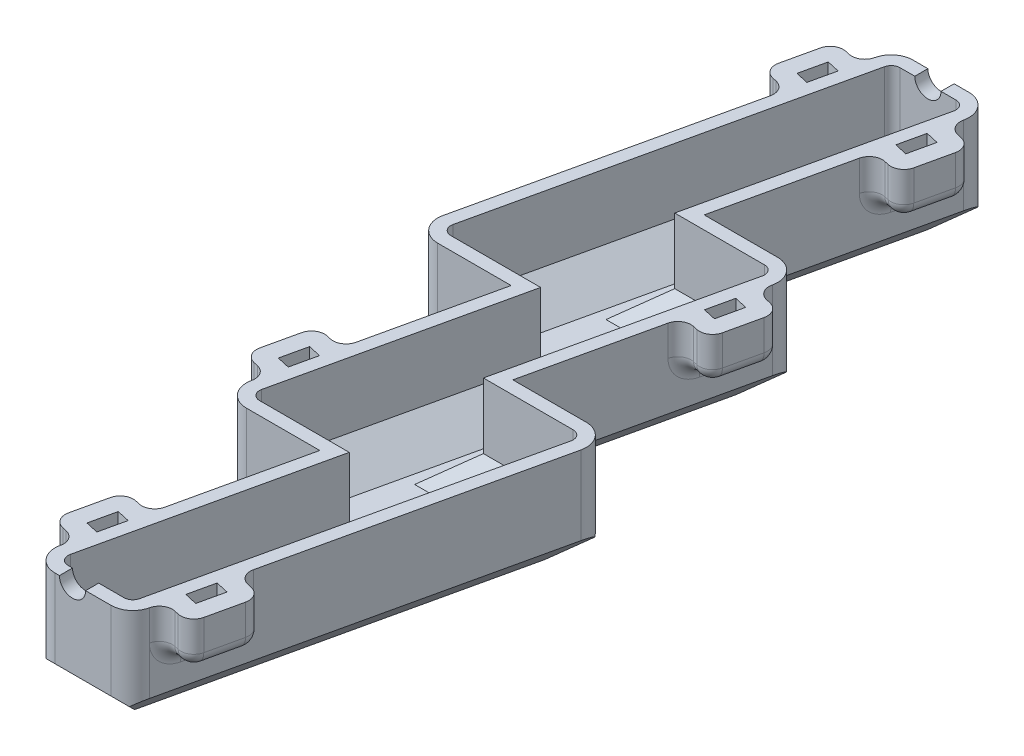
SolidWorks part; units mm, degrees
ref_plane "Front Plane" through (0, 0, 0) normal (0, 0, 1) x (1, 0, 0)
ref_plane "Top Plane" through (0, 0, 0) normal (0, 1, 0) x (1, 0, 0)
ref_plane "Right Plane" through (0, 0, 0) normal (1, 0, 0) x (0, 0, -1)
sketch "Sketch1" plane through (0, 0, 0) normal (0, 1, 0) x (1, 0, 0)
  line L12 (-1.3505, 45.3722) -> (21.7087, 45.3722)
  line L17 (-1.3505, 45.3722) -> (-21.7087, -45.3722)
  line L18 (21.7087, 45.3722) -> (1.3505, -45.3722)
  line L19 (-21.7087, -45.3722) -> (1.3505, -45.3722)
  line L20 (10.1791, 45.3722) -> (-10.1791, -45.3722) construction
  line L21 (12.1543, -100) -> (-10.905, -100)
  line L22 (12.1543, -100) -> (32.5125, -9.2556)
  line L23 (-10.905, -100) -> (9.4532, -9.2556)
  line L24 (32.5125, -9.2556) -> (9.4532, -9.2556)
  line L25 (0.6246, -100) -> (20.9828, -9.2556) construction
  line L26 (-12.1543, 100) -> (10.905, 100)
  line L27 (-12.1543, 100) -> (-32.5125, 9.2556)
  line L28 (10.905, 100) -> (-9.4532, 9.2556)
  line L29 (-32.5125, 9.2556) -> (-9.4532, 9.2556)
  line L30 (-0.6246, 100) -> (-20.9828, 9.2556) construction
  line L31 (-17.9611, -42.3722) -> (-1.051, -42.3722) construction
  line L32 (-17.9611, -42.3722) -> (1.051, 42.3722) construction
  line L33 (-1.051, -42.3722) -> (17.9611, 42.3722)
  line L34 (1.051, 42.3722) -> (17.9611, 42.3722) construction
  line L35 (9.5061, 42.3722) -> (17.556, 40.5662) construction
  line L36 (-9.4532, 9.2556) -> (9.4532, -9.2556) construction
  line L41 (1.3505, -45.3722) -> (20.2569, -63.8834) construction
  point P7 (0, 0)
  point P20 (9.5061, 42.3722)
  point P21 (-9.5061, -42.3722)
  point P26 (8.4551, 0)
  point P28 (0, 0)
  point P30 (10.8037, -54.6278)
  point P36 (10.8037, -54.6278)
  dimension "D1" = 93
  dimension "D2" = 16.5
  dimension "D3" = 85
  dimension "D4" = 3
  dimension "D5" = 3
  dimension "D6" = 200
extrude "Boss-Extrude1" add sketch "Sketch1" along normal blind 25
sketch "Sketch4" plane through (0, 25, 0) normal (0, 1, 0) x (1, 0, 0)
  line L8 (-9.7527, 97) -> (7.1574, 97)
  line L13 (-9.7527, 97) -> (-28.7648, 12.2556)
  line L18 (7.1574, 97) -> (-11.8547, 12.2556)
  line L19 (-28.7648, 12.2556) -> (-11.8547, 12.2556)
  line L20 (1.051, 42.3722) -> (17.9611, 42.3722)
  line L21 (1.051, 42.3722) -> (-17.9611, -42.3722)
  line L22 (17.9611, 42.3722) -> (-1.051, -42.3722)
  line L23 (-17.9611, -42.3722) -> (-1.051, -42.3722)
  line L24 (11.8547, -12.2556) -> (28.7648, -12.2556)
  line L25 (11.8547, -12.2556) -> (-7.1574, -97)
  line L30 (28.7648, -12.2556) -> (9.7527, -97)
  line L31 (-7.1574, -97) -> (9.7527, -97)
  line L34 (1.051, 42.3722) -> (-5.0982, 42.3722)
  line L35 (-11.8547, 12.2556) -> (-5.7056, 12.2556)
  line L36 (11.8547, -12.2556) -> (5.7056, -12.2556)
  line L37 (-1.051, -42.3722) -> (5.0982, -42.3722)
  line L39 (-12.1543, 100) -> (-32.5125, 9.2556) construction
  line L40 (10.905, 100) -> (-1.3505, 45.3722) construction
  line L41 (-9.4532, 9.2556) -> (-21.7087, -45.3722) construction
  line L42 (1.3505, -45.3722) -> (-10.905, -100) construction
  line L44 (-12.1543, 100) -> (10.905, 100) construction
  line L45 (-1.3505, 45.3722) -> (21.7087, 45.3722) construction
  line L46 (32.5125, -9.2556) -> (9.4532, -9.2556) construction
  line L47 (-32.5125, 9.2556) -> (-9.4532, 9.2556) construction
  dimension "D1" = 3
  dimension "D2" = 3
  dimension "D3" = 3
  dimension "D4" = 3
  dimension "D5" = 3
  dimension "D6" = 3
  dimension "D7" = 3
  dimension "D8" = 3
extrude "Cut-Extrude1" cut sketch "Sketch4" against normal blind 22 contours L13 L19 L18 L8 | L18 L35 L21 L34 | L21 L23 L22 L20 | L25 L31 L30 L24 | L22 L37 L25 L36
chamfer "Chamfer2" distance 7 angle 45 24 edges at (0.6246, 0, 100) (-4.7772, 0, 72.6861) (-10.1791, 0, 45.3722) (-15.581, 0, 18.0583) (-20.9828, 0, -9.2556) (-22.3334, 0, -54.6278) (-0.6246, 0, -100) (4.7772, 0, -72.6861) (10.1791, 0, -45.3722) (15.581, 0, -18.0583) (20.9828, 0, 9.2556) (22.3334, 0, 54.6278) (-19.2588, 3, -54.6278) (6.4315, 3, -42.3722) (17.2352, 3, 12.2556) (1.2977, 3, 97) (-1.0296, 3, 69.6861) (-6.4315, 3, 42.3722) (-11.8333, 3, 15.0583) (-17.2352, 3, -12.2556) (-1.2977, 3, -97) (1.0296, 3, -69.6861) (11.8333, 3, -15.0583) (19.2588, 3, 54.6278)
fillet "Fillet4" radius 5 8 edges at (12.1543, 16, 100) (-10.905, 16, 100) (-21.7087, 16, 45.3722) (-32.5125, 16, -9.2556) (-12.1543, 16, -100) (10.905, 16, -100) (21.7087, 16, -45.3722) (32.5125, 16, 9.2556)
fillet "Fillet5" radius 2 8 edges at (17.9611, 17.5, -42.3722) (9.7527, 17.5, 97) (-7.1574, 17.5, 97) (28.7648, 17.5, 12.2556) (-17.9611, 17.5, 42.3722) (-28.7648, 17.5, -12.2556) (-9.7527, 17.5, -97) (7.1574, 17.5, -97)
sketch "Sketch29" plane through (0, 25, 0) normal (0, 1, 0) x (1, 0, 0)
  line L0 (8.881, 90.9782) -> (8.0054, 87.0753)
  line L1 (8.881, 90.9782) -> (15.7112, 89.4459)
  line L2 (5.8163, 77.3178) -> (12.6466, 75.7855)
  line L3 (15.7112, 89.4459) -> (12.6466, 75.7855)
  line L4 (9.5377, 93.9055) -> (-1.3505, 45.3722) construction
  line L5 (-13.6872, 93.1673) -> (-14.5628, 89.2643)
  line L6 (-13.6872, 93.1673) -> (-20.5174, 94.6996)
  line L7 (-16.7518, 79.5068) -> (-23.582, 81.0392)
  line L8 (-20.5174, 94.6996) -> (-23.582, 81.0392)
  line L9 (-13.0304, 96.0945) -> (-31.1452, 15.3501) construction
  line L10 (19.6847, 36.3504) -> (18.8091, 32.4474)
  line L11 (19.6847, 36.3504) -> (26.515, 34.8181)
  line L12 (16.6201, 22.69) -> (23.4503, 21.1576)
  line L13 (26.515, 34.8181) -> (23.4503, 21.1576)
  line L14 (20.3414, 39.2777) -> (9.4532, -9.2556) construction
  line L15 (-19.6847, -36.3504) -> (-18.8091, -32.4474)
  line L16 (-19.6847, -36.3504) -> (-26.515, -34.8181)
  line L17 (-16.6201, -22.69) -> (-23.4503, -21.1576)
  line L18 (-26.515, -34.8181) -> (-23.4503, -21.1576)
  line L19 (-9.4532, 9.2556) -> (-20.3414, -39.2777) construction
  line L24 (13.0304, -96.0945) -> (31.1452, -15.3501) construction
  line L25 (-8.881, -90.9782) -> (-8.0054, -87.0753)
  line L26 (-8.881, -90.9782) -> (-15.7112, -89.4459)
  line L27 (-5.8163, -77.3178) -> (-12.6466, -75.7855)
  line L28 (-15.7112, -89.4459) -> (-12.6466, -75.7855)
  line L29 (1.3505, -45.3722) -> (-9.5377, -93.9055) construction
  line L30 (13.6872, -93.1673) -> (14.5628, -89.2643)
  line L31 (13.6872, -93.1673) -> (20.5174, -94.6996)
  line L32 (16.7518, -79.5068) -> (23.582, -81.0392)
  line L33 (20.5174, -94.6996) -> (23.582, -81.0392)
  line L35 (-14.5628, 89.2643) -> (-17.49, 89.921)
  line L36 (-15.8762, 83.4098) -> (-18.8034, 84.0665)
  line L37 (-17.49, 89.921) -> (-18.8034, 84.0665)
  line L39 (8.0054, 87.0753) -> (10.9326, 86.4185)
  line L40 (6.692, 81.2208) -> (9.6192, 80.5641)
  line L41 (10.9326, 86.4185) -> (9.6192, 80.5641)
  line L43 (18.8091, 32.4474) -> (21.7364, 31.7907)
  line L44 (17.4957, 26.593) -> (20.4229, 25.9363)
  line L45 (21.7364, 31.7907) -> (20.4229, 25.9363)
  line L47 (-17.4957, -26.593) -> (-20.4229, -25.9363)
  line L48 (-18.8091, -32.4474) -> (-21.7364, -31.7907)
  line L49 (-20.4229, -25.9363) -> (-21.7364, -31.7907)
  line L55 (-6.692, -81.2208) -> (-9.6192, -80.5641)
  line L56 (-8.0054, -87.0753) -> (-10.9326, -86.4185)
  line L57 (-9.6192, -80.5641) -> (-10.9326, -86.4185)
  line L59 (15.8762, -83.4098) -> (18.8034, -84.0665)
  line L60 (14.5628, -89.2643) -> (17.49, -89.921)
  line L61 (18.8034, -84.0665) -> (17.49, -89.921)
  line L62 (-15.8762, 83.4098) -> (-16.7518, 79.5068)
  line L63 (6.692, 81.2208) -> (5.8163, 77.3178)
  line L64 (-17.4957, -26.593) -> (-16.6201, -22.69)
  line L65 (-6.692, -81.2208) -> (-5.8163, -77.3178)
  line L66 (15.8762, -83.4098) -> (16.7518, -79.5068)
  line L67 (17.4957, 26.593) -> (16.6201, 22.69)
  point P25 (23.4503, -81.2212)
  point P26 (-12.0575, -86.0463)
  point P36 (-17.4957, 90.9782)
  point P76 (0, 0)
  dimension "D1" = 7
  dimension "D2" = 14
  dimension "D3" = 3
  dimension "D4" = 3
  dimension "D5" = 3
  dimension "D6" = 3
  dimension "D8" = 3
  dimension "D9" = 3
  dimension "D10" = 3
  dimension "D11" = 6
  dimension "D12" = 4
  dimension "D13" = 4
  dimension "D14" = 4
  dimension "D16" = 4
  dimension "D17" = 4
  dimension "D18" = 4
extrude "Boss-Extrude2" add sketch "Sketch29" against normal blind 10
fillet "Fillet6" radius 3 54 edges at (16.6201, 20, -22.69) (19.6847, 20, -36.3504) (5.8163, 20, -77.3178) (8.881, 20, -90.9782) (-13.6872, 20, -93.1673) (-16.7518, 20, -79.5068) (-16.6201, 20, 22.69) (-19.6847, 20, 36.3504) (-8.881, 20, 90.9782) (-5.8163, 20, 77.3178) (13.6872, 20, 93.1673) (16.7518, 20, 79.5068) (23.4503, 20, -21.1576) (20.0352, 15, -21.9238) (17.0579, 15, -24.6415) (19.2469, 15, -34.3989) (24.9826, 15, -27.9879) (23.0998, 15, -35.5843) (26.515, 20, -34.8181) (6.2542, 15, -79.2693) (8.4432, 15, -89.0267) (9.2315, 15, -76.5516) (12.6466, 20, -75.7855) (14.1789, 15, -82.6157) (15.7112, 20, -89.4459) (12.2961, 15, -90.2121) (-17.1023, 15, -93.9335) (-20.5174, 20, -94.6996) (-23.582, 20, -81.0392) (-20.1669, 15, -80.273) (-16.314, 15, -81.4583) (-22.0497, 15, -87.8694) (-14.125, 15, -91.2158) (-23.4503, 20, 21.1576) (-17.0579, 15, 24.6415) (-20.0352, 15, 21.9238) (-24.9826, 15, 27.9879) (-26.515, 20, 34.8181) (-19.2469, 15, 34.3989) (-23.0998, 15, 35.5843) (-12.6466, 20, 75.7855) (-15.7112, 20, 89.4459) (-14.1789, 15, 82.6157) (-8.4432, 15, 89.0267) (-12.2961, 15, 90.2121) (-9.2315, 15, 76.5516) (-6.2542, 15, 79.2693) (14.125, 15, 91.2158) (16.314, 15, 81.4583) (20.5174, 20, 94.6996) (17.1023, 15, 93.9335) (22.0497, 15, 87.8694) (23.582, 20, 81.0392) (20.1669, 15, 80.273)
sketch "Sketch30" plane through (0, 0, 100) normal (0, 0, 1) x (1, 0, 0)
  line L0 (8.1517, 25) -> (-4.659, 25) construction
  line L1 (-4.659, 25) -> (-4.659, 7) construction
  circle A0 centre (-0.659, 25) radius 3
  point P4 (0, 0)
  point P6 (0, 0)
  dimension "D1" = 6
  dimension "D2" = 4
extrude "Cut-Extrude2" cut sketch "Sketch30" against normal blind 10
sketch "Sketch31" plane through (0, 0, -100) normal (0, 0, -1) x (-1, 0, 0)
  line L0 (8.1517, 25) -> (-4.659, 25) construction
  circle A0 centre (1.7464, 25) radius 3
  point P4 (1.7464, 25)
  dimension "D1" = 6
extrude "Cut-Extrude3" cut sketch "Sketch31" against normal blind 10
